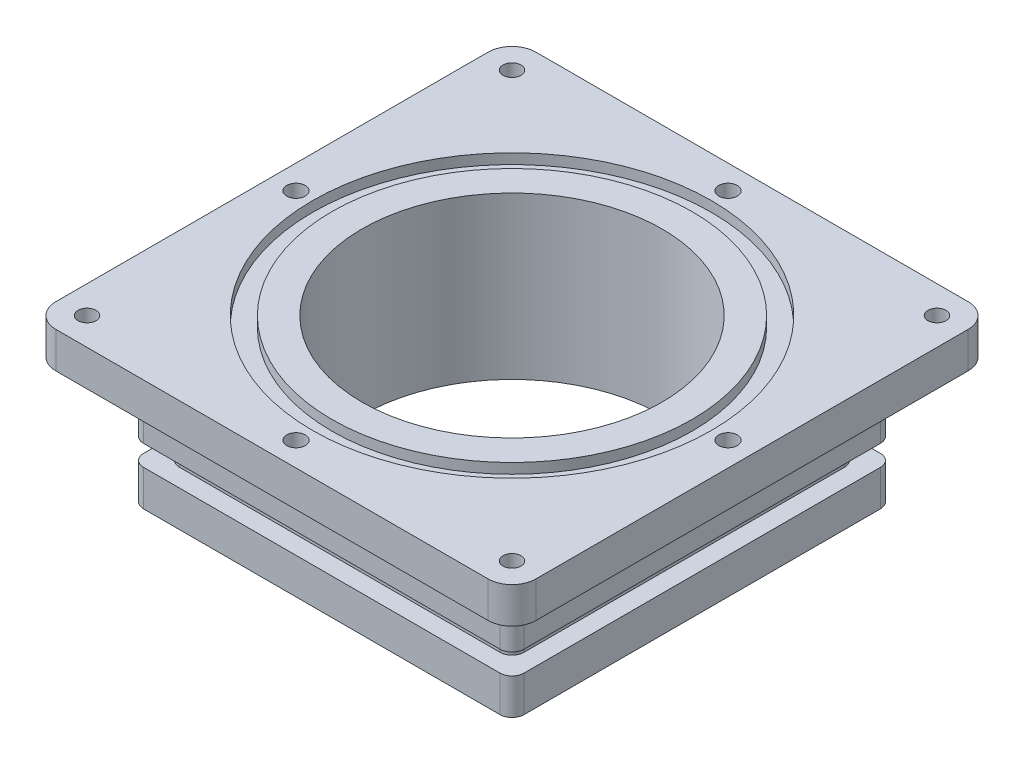
SolidWorks part; units mm, degrees
material "ABS"
ref_plane "前视基准面" through (0, 0, 0) normal (0, 0, 1) x (1, 0, 0)
ref_plane "上视基准面" through (0, 0, 0) normal (0, 1, 0) x (1, 0, 0)
ref_plane "右视基准面" through (0, 0, 0) normal (1, 0, 0) x (0, 0, -1)
ref_axis "基准轴1" through (0, 55, 0) along (0, -1, 0)
sketch "草图3" plane through (0, 0, 0) normal (0, 1, 0) x (1, 0, 0)
  line L1 (-40, 40) -> (40, 40)
  line L2 (-40, 40) -> (-40, -40)
  line L3 (-40, -40) -> (40, -40)
  line L4 (40, 40) -> (40, -40)
  line L5 (-40, 40) -> (40, -40) construction
  line L6 (-40, -40) -> (40, 40) construction
  point P0 (0, 0)
  dimension "D1" = 80
  dimension "D2" = 80
extrude "凸台-拉伸1" add sketch "草图3" along normal blind 6
ref_plane "基准面1" through (0, 0, 0) normal (0, -1, 0) x (-1, 0, 0)
sketch "草图4" plane through (0, 0, 0) normal (0, -1, 0) x (-1, 0, 0)
  line L1 (-31.7, 31.7) -> (31.7, 31.7)
  line L2 (-31.7, 31.7) -> (-31.7, -31.7)
  line L3 (-31.7, -31.7) -> (31.7, -31.7)
  line L4 (31.7, 31.7) -> (31.7, -31.7)
  line L5 (-31.7, 31.7) -> (31.7, -31.7) construction
  line L6 (-31.7, -31.7) -> (31.7, 31.7) construction
  point P0 (0, 0)
  dimension "D1" = 63.4
  dimension "D2" = 63.4
extrude "凸台-拉伸2" add sketch "草图4" along normal blind 4
ref_plane "基准面2" through (0, -4, 0) normal (0, -1, 0) x (-1, 0, 0)
sketch "草图5" plane through (0, -4, 0) normal (0, -1, 0) x (-1, 0, 0)
  line L1 (-28.7, 28.7) -> (28.7, 28.7)
  line L2 (-28.7, 28.7) -> (-28.7, -28.7)
  line L3 (-28.7, -28.7) -> (28.7, -28.7)
  line L4 (28.7, 28.7) -> (28.7, -28.7)
  line L5 (-28.7, 28.7) -> (28.7, -28.7) construction
  line L6 (-28.7, -28.7) -> (28.7, 28.7) construction
  point P0 (0, 0)
  dimension "D1" = 57.4
  dimension "D2" = 57.4
extrude "凸台-拉伸3" add sketch "草图5" along normal blind 3.45
ref_plane "基准面3" through (0, -7.45, 0) normal (0, -1, 0) x (-1, 0, 0)
sketch "草图6" plane through (0, -7.45, 0) normal (0, -1, 0) x (-1, 0, 0)
  line L1 (-31.7, -31.7) -> (31.7, -31.7)
  line L2 (-31.7, -31.7) -> (-31.7, 31.7)
  line L3 (-31.7, 31.7) -> (31.7, 31.7)
  line L4 (31.7, -31.7) -> (31.7, 31.7)
  line L5 (-31.7, -31.7) -> (31.7, 31.7) construction
  line L6 (-31.7, 31.7) -> (31.7, -31.7) construction
  point P0 (0, 0)
extrude "凸台-拉伸4" add sketch "草图6" along normal blind 4
ref_plane "基准面4" through (0, -11.45, 0) normal (0, -1, 0) x (-1, 0, 0)
sketch "草图7" plane through (0, -11.45, 0) normal (0, -1, 0) x (-1, 0, 0)
  line L1 (-28.7, -28.7) -> (28.7, -28.7)
  line L2 (-28.7, -28.7) -> (-28.7, 28.7)
  line L3 (-28.7, 28.7) -> (28.7, 28.7)
  line L4 (28.7, -28.7) -> (28.7, 28.7)
  line L5 (-28.7, -28.7) -> (28.7, 28.7) construction
  line L6 (-28.7, 28.7) -> (28.7, -28.7) construction
  point P0 (0, 0)
  dimension "D1" = 57.4
  dimension "D2" = 57.4
extrude "凸台-拉伸5" add sketch "草图7" along normal blind 3.45
ref_plane "基准面5" through (0, -14.9, 0) normal (0, -1, 0) x (-1, 0, 0)
sketch "草图8" plane through (0, -14.9, 0) normal (0, -1, 0) x (-1, 0, 0)
  line L1 (-31.7, -31.7) -> (31.7, -31.7)
  line L2 (-31.7, -31.7) -> (-31.7, 31.7)
  line L3 (-31.7, 31.7) -> (31.7, 31.7)
  line L4 (31.7, -31.7) -> (31.7, 31.7)
  line L5 (-31.7, -31.7) -> (31.7, 31.7) construction
  line L6 (-31.7, 31.7) -> (31.7, -31.7) construction
  point P0 (0, 0)
extrude "凸台-拉伸6" add sketch "草图8" along normal blind 6
ref_plane "基准面6" through (0, 6, 0) normal (0, 1, 0) x (1, 0, 0)
sketch "草图11" plane through (0, 6, 0) normal (0, 1, 0) x (1, 0, 0)
  circle A0 centre (0, 0) radius 25
  dimension "D1" = 50
extrude "切除-拉伸3" cut sketch "草图11" against normal through all and the other way through all
ref_plane "基准面7" through (0, 6, 0) normal (0, 1, 0) x (1, 0, 0)
sketch "草图12" plane through (0, 6, 0) normal (0, 1, 0) x (1, 0, 0)
  circle A0 centre (0, 0) radius 33.2
  circle A1 centre (0, 0) radius 30
  dimension "D1" = 66.4
  dimension "D2" = 60
extrude "切除-拉伸4" cut sketch "草图12" against normal blind 1.7
sketch "草图13" plane through (0, 6, 0) normal (0, 1, 0) x (1, 0, 0)
  line L0 (-40, 40) -> (40, 40) construction
  circle A0 centre (0, 36) radius 1.55
  dimension "D2" = 3.1
  dimension "D1" = 4
extrude "切除-拉伸5" cut sketch "草图13" against normal blind 6
pattern_circular "阵列(圆周)1" count 4 over 360 about axis through (0, 55, 0) along (0, -1, 0) of "切除-拉伸5"
sketch "草图14" plane through (0, 6, 0) normal (0, 1, 0) x (1, 0, 0)
  line L0 (-40, 40) -> (40, -40) construction
  circle A0 centre (-35.4038, 35.4038) radius 1.5
  dimension "D1" = 3
  dimension "D2" = 6.5
extrude "切除-拉伸6" cut sketch "草图14" against normal blind 6
pattern_circular "阵列(圆周)2" count 4 over 360 about axis through (0, 55, 0) along (0, -1, 0) of "切除-拉伸6"
ref_plane "基准面8" through (0, 0, 0) normal (0, -1, 0) x (-1, 0, 0)
sketch "草图15" plane through (0, 0, 0) normal (0, -1, 0) x (-1, 0, 0)
  line L1 (1.6159, 33.1996) -> (3.2332, 35.9992)
  line L2 (3.2332, 35.9992) -> (1.6173, 38.7996)
  line L3 (1.6173, 38.7996) -> (-1.6159, 38.8004)
  line L4 (-1.6159, 38.8004) -> (-3.2332, 36.0008)
  line L5 (-3.2332, 36.0008) -> (-1.6173, 33.2004)
  line L6 (-1.6173, 33.2004) -> (1.6159, 33.1996)
  line L7 (-37.69, 37.69) -> (-38.5268, 34.567)
  line L8 (-38.5268, 34.567) -> (-36.2406, 32.2808)
  line L9 (-36.2406, 32.2808) -> (-33.1176, 33.1176)
  line L10 (-33.1176, 33.1176) -> (-32.2808, 36.2406)
  line L11 (-32.2808, 36.2406) -> (-34.567, 38.5268)
  line L12 (-34.567, 38.5268) -> (-37.69, 37.69)
  circle A0 centre (0, 36) radius 2.8 construction
  circle A1 centre (-35.4038, 35.4038) radius 2.8 construction
  dimension "D1" = 5.6
  dimension "D2" = 5.6
extrude "切除-拉伸7" cut sketch "草图15" against normal blind 3
pattern_circular "阵列(圆周)3" count 4 over 360 about axis through (0, 55, 0) along (0, -1, 0) of "切除-拉伸7"
ref_plane "基准面9" through (0, -20.9, 0) normal (0, -1, 0) x (-1, 0, 0)
fillet "圆角1" radius 2 20 edges at (31.7, -2, 31.7) (28.7, -5.725, 28.7) (31.7, -9.45, 31.7) (28.7, -13.175, 28.7) (31.7, -17.9, 31.7) (31.7, -2, -31.7) (28.7, -5.725, -28.7) (31.7, -9.45, -31.7) (28.7, -13.175, -28.7) (31.7, -17.9, -31.7) (-31.7, -2, -31.7) (-28.7, -5.725, -28.7) (-31.7, -9.45, -31.7) (-28.7, -13.175, -28.7) (-31.7, -17.9, -31.7) (-31.7, -17.9, 31.7) (-28.7, -13.175, 28.7) (-31.7, -9.45, 31.7) (-28.7, -5.725, 28.7) (-31.7, -2, 31.7)
fillet "圆角2" radius 4 4 edges at (40, 3, 40) (40, 3, -40) (-40, 3, 40) (-40, 3, -40)
